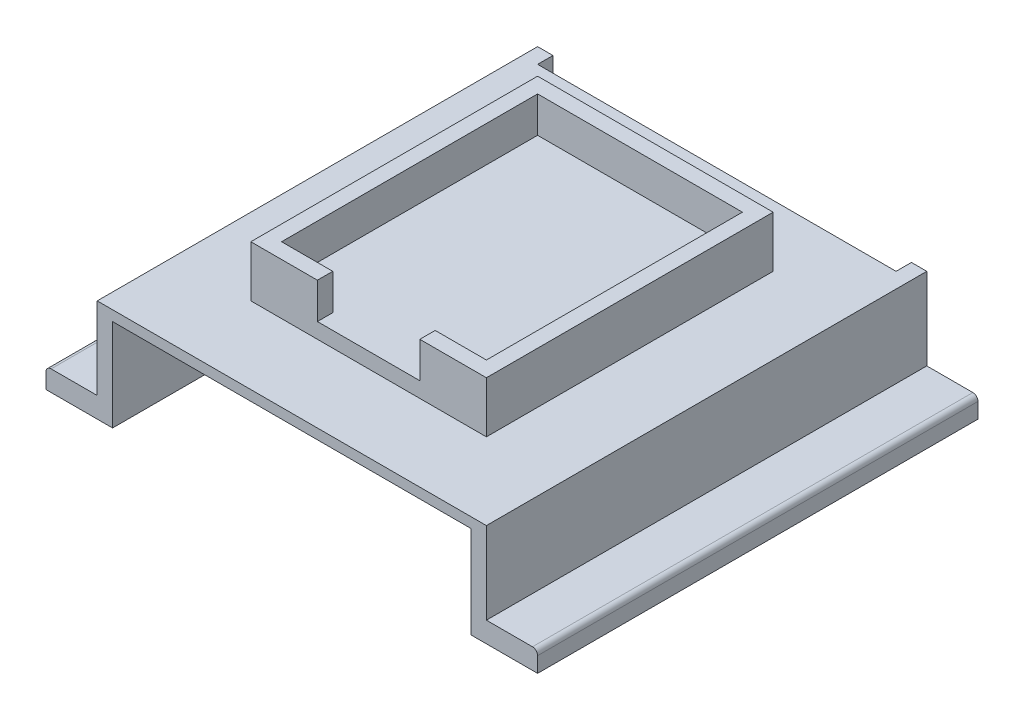
SolidWorks part; units mm, degrees
material "PEI"
ref_plane "Front Plane" through (0, 0, 0) normal (0, 0, 1) x (1, 0, 0)
ref_plane "Top Plane" through (0, 0, 0) normal (0, 1, 0) x (1, 0, 0)
ref_plane "Right Plane" through (0, 0, 0) normal (1, 0, 0) x (0, 0, -1)
sketch "Sketch1" plane through (0, 0, 0) normal (0, 1, 0) x (1, 0, 0)
  line L0 (11.5, 14) -> (-11.5, 14)
  line L1 (10, -12.5) -> (-10, -12.5)
  line L2 (10, -12.5) -> (10, 12.5)
  line L3 (10, 12.5) -> (-10, 12.5)
  line L4 (-10, -12.5) -> (-10, 12.5)
  line L5 (10, -12.5) -> (-10, 12.5) construction
  line L6 (10, 12.5) -> (-10, -12.5) construction
  line L7 (-11.5, -14) -> (-11.5, 14)
  line L8 (11.5, -14) -> (-11.5, -14)
  line L9 (11.5, -14) -> (11.5, 14)
  point P0 (0, 0)
  dimension "D1" = 20
  dimension "D2" = 25
  dimension "D3" = 1.5
extrude "Boss-Extrude1" add sketch "Sketch1" along normal blind 5
extrude "Boss-Extrude2" add sketch "Sketch1<3>" along normal blind 1.5 contours L4 L1 L2 L3 region at (0, 0, 0)
sketch "Sketch1<3>" plane through (0, 0, 0) normal (0, 1, 0) x (1, 0, 0) same geometry as "Sketch1"
sketch "Sketch3" plane through (0, 0, 14) normal (0, 0, 1) x (1, 0, 0)
  line L0 (0, 0) -> (0, 5)
  line L1 (5, 0) -> (5, 5)
  line L2 (-5, 0) -> (-5, 5)
  line L3 (-5, 5) -> (5, 5)
  line L4 (-11.5, 0) -> (11.5, 0)
  line L5 (11.5, 0) -> (11.5, 5)
  line L6 (11.5, 5) -> (-11.5, 5)
  line L7 (-11.5, 5) -> (-11.5, 0)
  line L8 (-11.5, 0) -> (11.5, 0)
  line L9 (11.5, 0) -> (11.5, 5)
  line L10 (11.5, 5) -> (-11.5, 5)
  line L11 (-11.5, 5) -> (-11.5, 0)
  line L12 (-5, 1.5) -> (5, 1.5)
  line M10 (11.5, 5) -> (-11.5, 5)
  dimension "D4" = 3.5
  dimension "D1" = 0
  dimension "D2" = 5
  dimension "D3" = 5
extrude "Cut-Extrude1" cut sketch "Sketch3" against normal blind 5 contours L2 L12 L0 M10 | L0 L12 L1 M10 region at (-2.5, 3.25, 14) region at (2.5, 3.25, 14)
sketch "Sketch4" plane through (0, 0, 0) normal (0, -1, 0) x (1, 0, 0)
  line L0 (19, 21.5) -> (-19, 21.5)
  line L1 (17.5, -20) -> (-17.5, -20)
  line L2 (17.5, -20) -> (17.5, 20)
  line L3 (17.5, 20) -> (-17.5, 20)
  line L4 (11.5, -14) -> (11.5, 14)
  line L5 (11.5, 14) -> (-11.5, 14)
  line L6 (-11.5, 14) -> (-11.5, -14)
  line L7 (-11.5, -14) -> (11.5, -14)
  line L8 (11.5, -14) -> (11.5, 14)
  line L9 (11.5, 14) -> (-11.5, 14)
  line L10 (-11.5, 14) -> (-11.5, -14)
  line L11 (-11.5, -14) -> (11.5, -14)
  line L12 (-17.5, -20) -> (-17.5, 20)
  line L13 (17.5, -20) -> (-17.5, 20) construction
  line L14 (17.5, 20) -> (-17.5, -20) construction
  line L15 (-19, -21.5) -> (-19, 21.5)
  line L16 (19, -21.5) -> (-19, -21.5)
  line L17 (19, -21.5) -> (19, 21.5)
  line L18 (-17.5, 20) -> (-17.5, 21.5)
  line L19 (17.5, 20) -> (17.5, 21.5)
  line L20 (-17.5, -20) -> (-17.5, -21.5)
  line L21 (17.5, -20) -> (17.5, -21.5)
  point P2 (0, 0)
  line M7 (11.5, -14) -> (11.5, 14)
  line M8 (11.5, 14) -> (-11.5, 14)
  line M9 (-11.5, 14) -> (-11.5, -14)
  line M10 (-11.5, -14) -> (11.5, -14)
  dimension "D2" = 35
  dimension "D3" = 40
  dimension "D1" = 0
  dimension "D4" = 1.5
extrude "Boss-Extrude3" add sketch "Sketch4" along normal blind 10 contours L20 L12 L18 L0 L15 L16 | L2 L21 L16 L17 L0 L19 region at (18.25, 0, 0) region at (-18.25, 0, 0)
extrude "Boss-Extrude4" add sketch "Sketch4<4>" along normal blind 1 contours L3 L19 L0 L18 | L12 L1 L2 L3 M7 M10 M9 M8 | M10 M7 M8 M9 region at (0, 0, 20.75) region at (16.9685, 0, 0) region at (0, 0, 0)
sketch "Sketch4<4>" plane through (0, 0, 0) normal (0, -1, 0) x (1, 0, 0) same geometry as "Sketch4"
sketch "Sketch5" plane through (-19, 0, 0) normal (-1, 0, 0) x (0, 0, 1)
  line L1 (-21.5, -10) -> (21.5, -10)
  line L2 (-21.5, -10) -> (-21.5, -8)
  line L3 (-21.5, -8) -> (21.5, -8)
  line L4 (21.5, 0) -> (-21.5, 0)
  line L5 (-21.5, 0) -> (-21.5, -10)
  line L6 (-21.5, -10) -> (21.5, -10)
  line L7 (21.5, -10) -> (21.5, 0)
  line L8 (21.5, 0) -> (-21.5, 0)
  line L9 (-21.5, 0) -> (-21.5, -10)
  line L10 (-21.5, -10) -> (21.5, -10)
  line L11 (21.5, -10) -> (21.5, 0)
  line L12 (21.5, -10) -> (21.5, -8)
  line M8 (-21.5, 0) -> (-21.5, -10)
  line M9 (-21.5, -10) -> (21.5, -10)
  line M10 (21.5, -10) -> (21.5, 0)
  dimension "D2" = 2
  dimension "D1" = 0
extrude "Boss-Extrude5" add sketch "Sketch5" along normal blind 5 contours L3 M8 M9 M10 region at (-19, -9, 0)
mirror "Mirror1" about plane through (0, 0, 0) normal (1, 0, 0) of "Boss-Extrude5"
fillet "Fillet1" radius 0.5 2 edges at (24, -8, 0) (-24, -8, 0)
